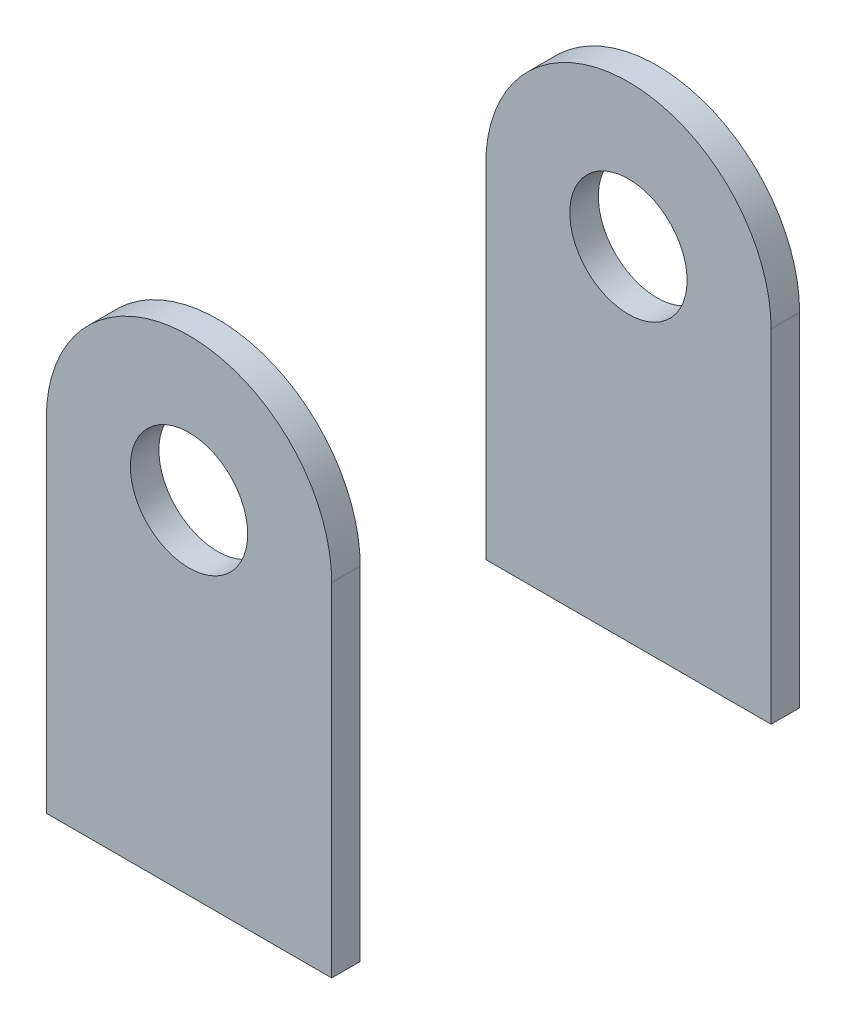
SolidWorks part; units mm, degrees
material "AISI 4130 Steel, normalized at 870C"
ref_plane "Front Plane" through (0, 0, 0) normal (0, 0, 1) x (1, 0, 0)
ref_plane "Top Plane" through (0, 0, 0) normal (0, 1, 0) x (1, 0, 0)
ref_plane "Right Plane" through (0, 0, 0) normal (1, 0, 0) x (0, 0, -1)
sketch "Sketch1" plane through (0, 0, 0) normal (0, 0, 1) x (1, 0, 0)
  line L0 (7.9375, 0) -> (7.9375, -19.05)
  line L1 (7.9375, -19.05) -> (-7.9375, -19.05)
  line L2 (-7.9375, -19.05) -> (-7.9375, 0)
  line L3 (0, 0) -> (0, -19.05) construction
  circle A0 centre (0, 0) radius 3.2639
  circle A1 centre (0, 0) radius 7.9375
  dimension "D1" = 6.5278
  dimension "D2" = 15.875
  dimension "D3" = 19.05
extrude "Boss-Extrude1" add sketch "Sketch1" along normal blind 1.5875 from offset 11.43 contours A1 A0 | A1 L2 L1 L0 | L3 A1 L2 L1 region at (5.4539, -5.4539, 0) region at (4.2606, -12.5196, 0) region at (-4.2606, -12.5196, 0)
extrude "Boss-Extrude2" add sketch "Sketch1<4>" against normal blind 1.5875 from offset 11.43 separate body contours A1 A0 | A1 L2 L1 L0 | L3 A1 L2 L1 region at (5.4539, -5.4539, 0) region at (4.2606, -12.5196, 0) region at (-4.2606, -12.5196, 0) offset against normal yes
sketch "Sketch1<4>" plane through (0, 0, 0) normal (0, 0, 1) x (1, 0, 0) same geometry as "Sketch1"
equation "\"Width Between Tabs\"= .9"
equation "\"Tab Thickness\"= 1 / 16"
equation "\"D19@Boss-Extrude1\"=\"Width Between Tabs\"/2"
equation "\"D1@Boss-Extrude1\"=\"Tab Thickness\""
equation "\"D19@Boss-Extrude2\"=\"Width Between Tabs\"/2"
equation "\"D1@Boss-Extrude2\"=\"Tab Thickness\""
equation "\"Hole Diameter\"= .257"
equation "\"D1@Sketch1\"=\"Hole Diameter\""
